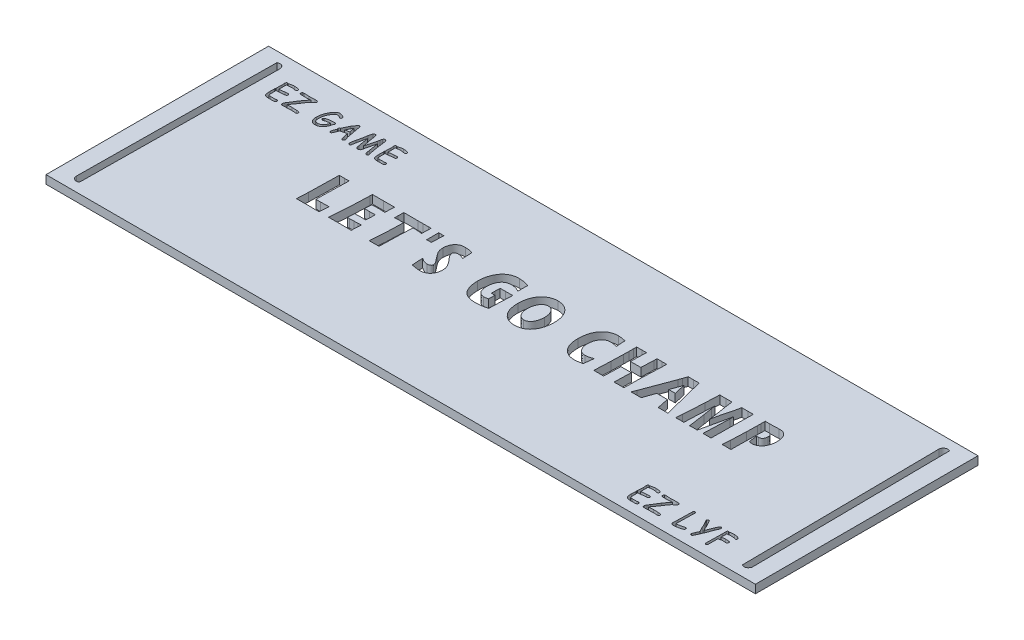
SolidWorks part; units mm, degrees
ref_plane "Front Plane" through (0, 0, 0) normal (0, 0, 1) x (1, 0, 0)
ref_plane "Top Plane" through (0, 0, 0) normal (0, 1, 0) x (1, 0, 0)
ref_plane "Right Plane" through (0, 0, 0) normal (1, 0, 0) x (0, 0, -1)
sketch "Sketch1" plane through (0, 0, 0) normal (0, 1, 0) x (1, 0, 0)
  line L1 (-127.5, -40) -> (127.5, -40)
  line L2 (-127.5, -40) -> (-127.5, 40)
  line L3 (-127.5, 40) -> (127.5, 40)
  line L4 (127.5, -40) -> (127.5, 40)
  line L5 (-127.5, -40) -> (127.5, 40) construction
  line L6 (-127.5, 40) -> (127.5, -40) construction
  point P0 (0, 0)
  dimension "D1" = 80
  dimension "D2" = 255
extrude "Boss-Extrude1" add sketch "Sketch1" along normal blind 3
sketch "Sketch2" plane through (0, 3, 0) normal (0, 1, 0) x (1, 0, 0)
  text T0 "LET'S GO CHAMP" font "Eras Bold ITC" height 15
extrude "Cut-Extrude1" cut sketch "Sketch2" against normal up to next
sketch "Sketch3" plane through (0, 3, 0) normal (0, 1, 0) x (1, 0, 0)
  line L0 (127.5, 40) -> (-127.5, 40) construction
  line L1 (-127.5, 40) -> (-127.5, -40) construction
  line L2 (-127.5, -40) -> (127.5, -40) construction
  line L4 (-118.4, 35) -> (-119.1375, -36.3476)
  line L5 (-121.6, -35) -> (-120.8625, 36.3476)
  line L6 (127.5, -40) -> (127.5, 40) construction
  line L7 (118.4, 35) -> (119.1375, -36.3476)
  line L10 (121.6, -35) -> (120.8625, 36.3476)
  arc A0 (-118.4, 35) -> (-120.8625, 36.3476) centre (-120, 35) ccw
  arc A3 (-121.6, -35) -> (-119.1375, -36.3476) centre (-120, -35) ccw
  arc A4 (120.8625, 36.3476) -> (118.4, 35) centre (120, 35) ccw
  arc A5 (119.1375, -36.3476) -> (121.6, -35) centre (120, -35) ccw
  dimension "D1" = 3.2
  dimension "D6" = 3.2
  dimension "D7" = 5
  dimension "D8" = 7.5
  dimension "D9" = 7.5
  dimension "D10" = 5
  dimension "D2" = 5
  dimension "D3" = 7.5
  dimension "D4" = 7.5
  dimension "D5" = 5
extrude "Cut-Extrude2" cut sketch "Sketch3" against normal up to next (3 mm away)
sketch "Sketch4" plane through (0, 3, 0) normal (0, 1, 0) x (1, 0, 0)
  text T0 "EZ GAME" font "Comic Sans MS" height 7.5
extrude "Cut-Extrude3" cut sketch "Sketch4" against normal up to next (3 mm away)
sketch "Sketch5" plane through (0, 3, 0) normal (0, 1, 0) x (1, 0, 0)
  text T0 "EZ LYF" font "Comic Sans MS" height 7.5
extrude "Cut-Extrude4" cut sketch "Sketch5" against normal up to next (3 mm away)
